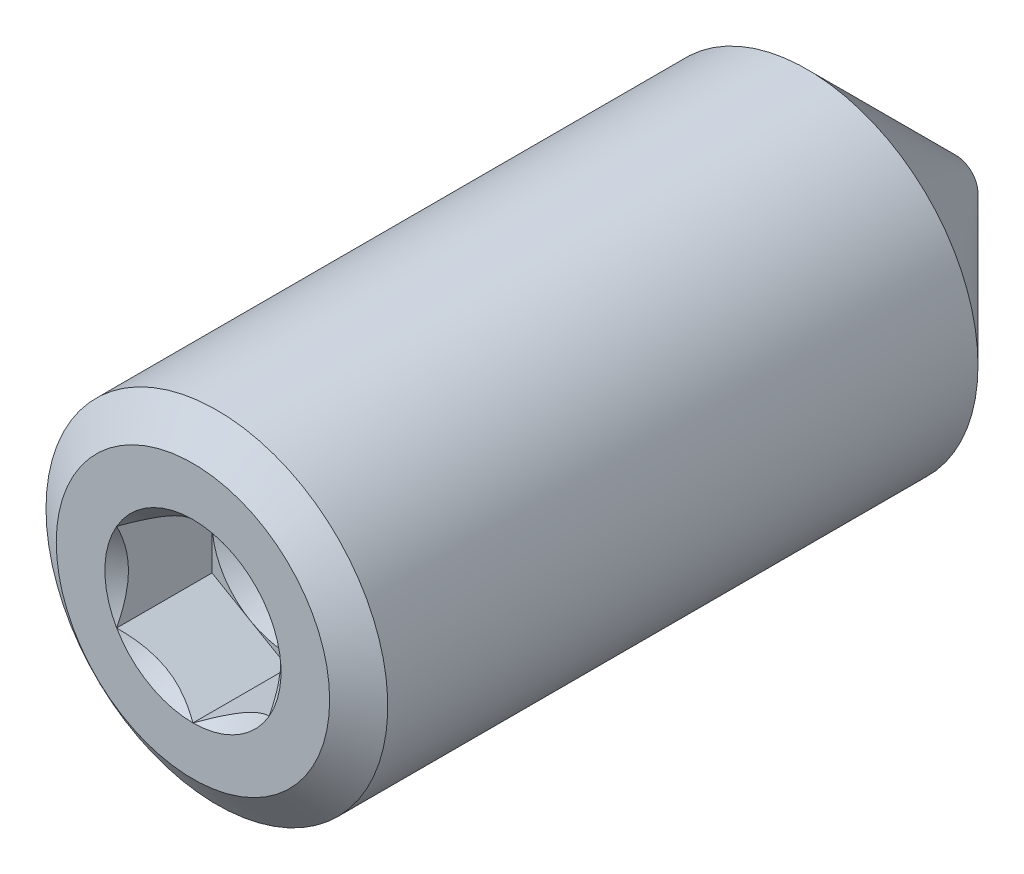
SolidWorks part; units mm, degrees
ref_plane "Front" through (0, 0, 0) normal (0, 0, 1) x (1, 0, 0)
ref_plane "Top" through (0, 0, 0) normal (0, 1, 0) x (1, 0, 0)
ref_plane "Right" through (0, 0, 0) normal (1, 0, 0) x (0, 0, -1)
sketch "Sketch22" plane through (0, 0, 0) normal (1, 0, 0) x (0, 0, -1)
  line L0 (-3.175, 0) -> (-3.175, 1.1379)
  line L1 (-3.175, 1.1379) -> (-2.9758, 1.4224)
  line L2 (-2.9758, 1.4224) -> (1.9375, 1.4224)
  line L3 (1.9375, 1.4224) -> (3.175, 0.1849)
  line L4 (-3.175, 1.1379) -> (-3.175, -1.1379) construction
  line L5 (3.175, 0) -> (-3.175, 0)
  line L6 (0, 1.4224) -> (0, -1.4224) construction
  line L8 (3.175, 0.1849) -> (3.175, 0)
  line L9 (-3.175, -1.4224) -> (3.175, -1.4224) construction
  line L10 (3.175, 0.1849) -> (3.175, -0.1849) construction
  line L11 (3.175, -0.1849) -> (1.9375, -1.4224) construction
  line L13 (3.175, 0.1849) -> (2.9901, 0) construction
  line L15 (2.9901, 0) -> (3.175, -0.1849) construction
  dimension "D3" = 35
  dimension "D7" = 2.2758
  dimension "Dia" = 2.8448
  dimension "Length" = 6.35
  dimension "D2" = 0.3698
  dimension "D1" = 90
  dimension "D4" = 90
revolve "Revolve1" add sketch "Sketch22" angle 360 about L5
ref_plane "Plane1" through (0, 0, -3.175) normal (0, 0, 1) x (1, 0, 0)
sketch "Sketch27" plane through (0, 0, -3.175) normal (0, 0, 1) x (1, 0, 0)
  circle A0 centre (0, 0) radius 1.4224 construction
  circle A1 centre (0, 0) radius 1.4224
curve "Helix/Spiral1" [suppressed] pitch 0.6195 height 6.9695 turns 11.25
sketch "Sketch28" plane through (0, 0, 0) normal (1, 0, 0) x (0, 0, -1)
  line L0 (3.175, 1.4224) -> (3.7171, 1.4224)
  line L1 (3.7171, 1.4224) -> (3.4848, 1.02)
  line L2 (3.4848, 1.02) -> (3.4073, 1.02)
  line L3 (3.4073, 1.02) -> (3.175, 1.4224)
  line L4 (3.2912, 1.2212) -> (3.6009, 1.2212) construction
  line L6 (-2.9758, 1.4224) -> (1.9375, 1.4224) construction
  line L7 (3.175, 1.6085) -> (3.175, -1.6085) construction
  dimension "D1" = 0.0774
  dimension "D3" = 60
  dimension "D2" = 0.3098
sweep "Cut-Sweep2" [suppressed] cut profiles "Sketch28" path "Helix/Spiral1"
sketch "Sketch23" plane through (0, 0, 3.175) normal (0, 0, 1) x (1, 0, 0)
  line L1 (0, 0.7332) -> (-0.635, 0.3666)
  line L2 (-0.635, 0.3666) -> (-0.635, -0.3666)
  line L3 (-0.635, -0.3666) -> (0, -0.7332)
  line L4 (0, -0.7332) -> (0.635, -0.3666)
  line L5 (0.635, -0.3666) -> (0.635, 0.3666)
  line L6 (0.635, 0.3666) -> (0, 0.7332)
  circle A0 centre (0, 0) radius 0.635 construction
  dimension "Hex" = 1.27
extrude "Cut-Extrude10" cut sketch "Sketch23" against normal blind 0.7937
sketch "Sketch24" plane through (0, 0, 3.175) normal (0, 0, 1) x (1, 0, 0)
  circle A0 centre (0, 0) radius 0.7332
extrude "Cut-Extrude11" cut sketch "Sketch24" against normal through all draft 45
sketch "Sketch26" plane through (0, 0, 2.3812) normal (0, 0, 1) x (1, 0, 0)
  circle A0 centre (0, 0) radius 0.635 construction
  circle A1 centre (0, 0) radius 0.635
extrude "Cut-Extrude12" cut sketch "Sketch26" against normal through all draft 60
sketch "Sketch30" plane through (0, 0, 0) normal (1, 0, 0) x (0, 0, -1)
  line L0 (-2.9758, 1.4224) -> (1.9375, 1.4224) construction
  line L1 (-3.175, 0) -> (-3.175, 1.1379) construction
  line L3 (-3.175, -1.4224) -> (3.175, -1.4224) construction
  point P0 (-3.175, 1.4224)
  point P1 (1.9375, 1.4224)
  point P2 (1.9375, -1.4224)
  point P11 (1.0082, -1.4224)
  dimension "D1" = 0.9293
equation "\"D7@Sketch22\"=\"Dia@Sketch22\"*.8"
equation "\"D1@Sketch28\" = \"D4@Helix/Spiral1\" * .125"
equation "\"D3@Helix/Spiral1\" = \"Length@Sketch22\" + \"D4@Helix/Spiral1\""
equation "\"D1@Sketch30\" = \"D4@Helix/Spiral1\" * 1.5"
equation "\"hex Depth@Cut-Extrude10\" = \"Hex@Sketch23\" * .625"
equation "\"D2@Sketch28\" = \"D4@Helix/Spiral1\" * .5"
equation "\"D2@Sketch22\" = \"Dia@Sketch22\" * .13"
equation "\"D4@Sketch22\" = \"D1@Sketch22\""
